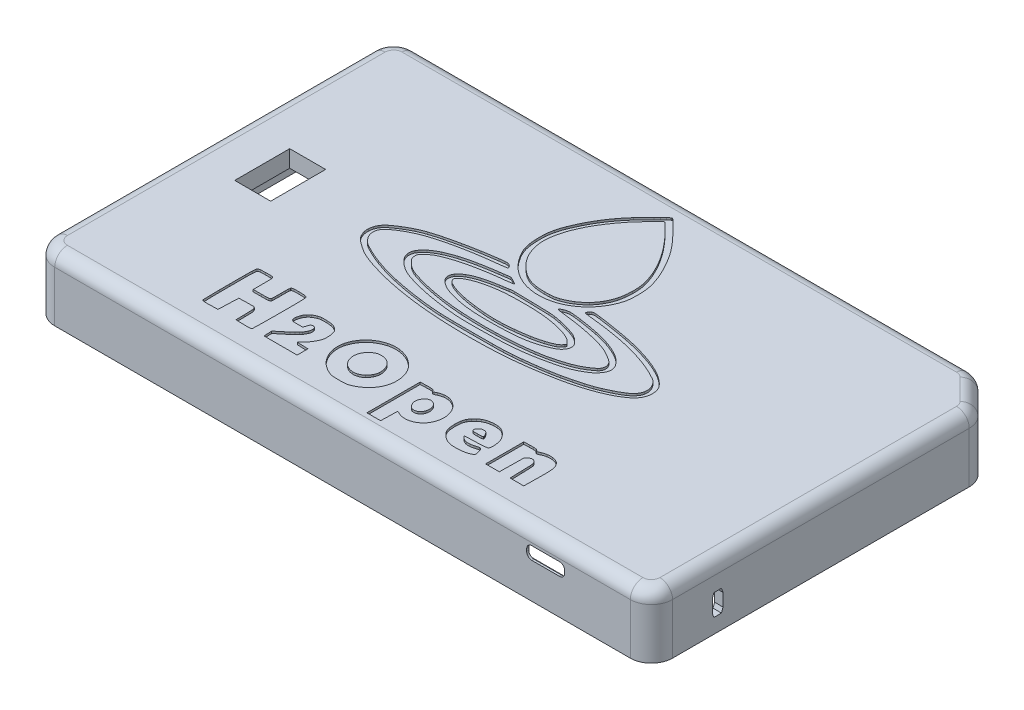
SolidWorks part; units mm, degrees
ref_plane "Front Plane" through (0, 0, 0) normal (0, 0, 1) x (1, 0, 0)
ref_plane "Top Plane" through (0, 0, 0) normal (0, 1, 0) x (1, 0, 0)
ref_plane "Right Plane" through (0, 0, 0) normal (1, 0, 0) x (0, 0, -1)
sketch "Sketch1" plane through (0, 0, 0) normal (0, 1, 0) x (1, 0, 0)
  line L0 (-69.085, -42.56) -> (-69.085, 42.56)
  line L1 (-69.085, 42.56) -> (69.085, 42.56)
  line L2 (-69.085, -42.56) -> (76.995, -42.56)
  line L3 (69.085, 42.56) -> (76.9975, 34.6475)
  line L4 (76.9975, 34.6475) -> (76.995, -42.56)
  point P2 (-69.085, 0)
  point P4 (0, 42.56)
  dimension "D1" = 85.12
  dimension "D2" = 138.17
  dimension "D3" = 146.08
  dimension "D4" = 11.19
  dimension "D5" = 45
extrude "Boss-Extrude1" add sketch "Sketch1" along normal blind 15
sketch "Sketch2" plane through (0, 0, 0) normal (0, -1, 0) x (1, 0, 0)
  line L29 (74.9951, 40.56) -> (-67.085, 40.56)
  line L30 (-67.085, 40.56) -> (-67.085, -40.56)
  line L31 (-67.085, -40.56) -> (68.2566, -40.56)
  line L32 (68.2566, -40.56) -> (74.9975, -33.8191)
  line L33 (74.9975, -33.8191) -> (74.9951, 40.56)
  line L34 (74.9951, 40.56) -> (-67.085, 40.56)
  line L35 (-67.085, 40.56) -> (-67.085, -40.56)
  line L36 (-67.085, -40.56) -> (68.2566, -40.56)
  line L37 (68.2566, -40.56) -> (74.9975, -33.8191)
  line L38 (74.9975, -33.8191) -> (74.9951, 40.56)
  dimension "D1" = 2
extrude "Cut-Extrude1" cut sketch "Sketch2" against normal blind 11
sketch "Sketch3" plane through (0, 11, 0) normal (0, -1, 0) x (1, 0, 0)
  line L0 (74.9951, 40.56) -> (-67.085, 40.56) construction
  line L1 (-67.085, 40.56) -> (-67.085, -40.56) construction
  line L2 (-67.085, -40.56) -> (68.2566, -40.56) construction
  line L3 (74.9975, -33.8191) -> (74.9951, 40.56) construction
  circle A0 centre (-65.585, 39.06) radius 1
  circle A1 centre (-65.585, -39.06) radius 1
  circle A2 centre (73.4951, 39.06) radius 1
  circle A3 centre (-65.585, -39.06) radius 1.375
  circle A4 centre (-65.585, 39.06) radius 1.375
  circle A5 centre (73.4951, 39.06) radius 1.375
  dimension "D1" = 2
  dimension "D6" = 2
  dimension "D7" = 2
  dimension "D10" = 2.75
  dimension "D11" = 2.75
  dimension "D12" = 2.75
  dimension "D2" = 1.5
  dimension "D3" = 1.5
  dimension "D4" = 1.5
  dimension "D5" = 1.5
  dimension "D8" = 1.5
  dimension "D9" = 1.5
extrude "Boss-Extrude7" add sketch "Sketch3" along normal blind 5
fillet "Fillet2" radius 3 5 edges at (-69.085, 15, 0) (0, 15, -42.56) (73.0413, 15, -38.6037) (76.9963, 15, 3.9563) (3.955, 15, 42.56)
fillet "Fillet3" radius 5 10 edges at (-69.085, 6, 42.56) (-68.2063, 14.1213, 41.6813) (-69.085, 6, -42.56) (-68.2063, 14.1213, -41.6813) (69.085, 6, -42.56) (68.721, 14.1213, -41.6813) (76.9975, 6, -34.6475) (76.1188, 14.1213, -34.2835) (76.995, 6, 42.56) (76.1163, 14.1213, 41.6813)
sketch "Sketch4" plane through (0, 15, 0) normal (0, 1, 0) x (1, 0, 0)
  line L0 (-5.2574, 6.3363) -> (-5.9266, 6.2402)
  line L1 (-3.051, 3.67) -> (-3.5719, 3.5824)
  line L2 (-3.5719, 3.5824) -> (-4.1882, 3.4796)
  line L3 (-4.1882, 3.4796) -> (-4.838, 3.3722)
  line L4 (-34.9308, -34.9317) -> (-33.1587, -34.8829)
  line L5 (-33.1587, -34.8829) -> (-33.0736, -32.5016)
  line L6 (-33.0736, -32.5016) -> (-32.9886, -30.1203)
  line L7 (-32.9886, -30.1203) -> (-31.0796, -30.0722)
  line L8 (-28.9481, -32.8418) -> (-28.9063, -34.8829)
  line L9 (-28.9063, -34.8829) -> (-27.1342, -34.9317)
  line L10 (-31.1357, -26.6333) -> (-33.0736, -26.6333)
  line L11 (-33.0736, -26.6333) -> (-33.0736, -24.2702)
  line L12 (-20.7371, -28.5044) -> (-19.4984, -28.5044)
  line L13 (-19.4984, -28.5044) -> (-19.2696, -27.7815)
  line L14 (-20.6874, -31.5828) -> (-22.3736, -32.9615)
  line L15 (-22.3736, -32.9615) -> (-22.3231, -33.9222)
  line L16 (-22.3231, -33.9222) -> (-22.2727, -34.8829)
  line L17 (-22.2727, -34.8829) -> (-18.3605, -34.8829)
  line L18 (-18.3605, -34.8829) -> (-14.4483, -34.8829)
  line L19 (-14.4483, -34.8829) -> (-14.4483, -33.6072)
  line L20 (-14.4483, -33.6072) -> (-14.4483, -32.3315)
  line L21 (-14.4483, -32.3315) -> (-15.757, -32.282)
  line L22 (-15.757, -32.282) -> (-17.0657, -32.2325)
  line L23 (-17.0657, -32.2325) -> (-16.3009, -31.4343)
  line L24 (6.8965, -25.8171) -> (5.6228, -25.8679)
  line L25 (5.6228, -25.8679) -> (5.6228, -32.1614)
  line L26 (5.6228, -32.1614) -> (5.6228, -38.4549)
  line L27 (5.6228, -38.4549) -> (7.2387, -38.4549)
  line L28 (7.2387, -38.4549) -> (8.8546, -38.4549)
  line L29 (8.8546, -38.4549) -> (8.9024, -36.467)
  line L30 (8.9024, -36.467) -> (8.9502, -34.479)
  line L31 (8.9502, -34.479) -> (9.6678, -34.8048)
  line L32 (22.2281, -32.1052) -> (21.7817, -31.6511)
  line L33 (21.7817, -31.6511) -> (24.3715, -31.5617)
  line L34 (31.39, -25.8171) -> (30.1163, -25.8679)
  line L35 (30.1163, -25.8679) -> (30.1163, -30.3754)
  line L36 (30.1163, -30.3754) -> (30.1163, -34.8829)
  line L37 (30.1163, -34.8829) -> (31.7322, -34.8829)
  line L38 (31.7322, -34.8829) -> (33.3481, -34.8829)
  line L39 (33.3481, -34.8829) -> (33.3946, -31.958)
  line L40 (33.3946, -31.958) -> (33.4411, -29.0331)
  line L41 (33.4411, -29.0331) -> (33.8853, -28.6837)
  line L42 (35.8145, -31.9334) -> (35.8995, -34.8829)
  line L43 (35.8995, -34.8829) -> (37.5154, -34.8829)
  line L44 (37.5154, -34.8829) -> (39.1313, -34.8829)
  line L45 (39.1313, -34.8829) -> (39.1776, -31.598)
  arc A0 (-0.4595, 35.4935) -> (-2.8347, 33.0017) centre (37.0957, -2.6811) ccw
  arc A1 (-2.8347, 33.0017) -> (-4.8098, 30.5893) centre (24.077, 8.9527) ccw
  arc A2 (-4.8098, 30.5893) -> (-6.4501, 28.173) centre (20.3393, 11.7523) ccw
  arc A3 (-6.4501, 28.173) -> (-7.817, 25.6706) centre (17.8976, 13.2489) ccw
  arc A4 (-7.817, 25.6706) -> (-8.9328, 23.1457) centre (28.8643, 7.9514) ccw
  arc A5 (-8.9328, 23.1457) -> (-9.5775, 21.1252) centre (4.4879, 17.7506) ccw
  arc A6 (-9.5775, 21.1252) -> (-9.8723, 19.202) centre (1.7861, 18.3988) ccw
  arc A7 (-9.8723, 19.202) -> (-9.895, 17.0096) centre (8.8523, 17.912) ccw
  arc A8 (-9.895, 17.0096) -> (-9.7498, 15.4268) centre (8.4005, 17.8902) ccw
  arc A9 (-9.7498, 15.4268) -> (-9.4745, 14.1492) centre (-1.3714, 16.564) ccw
  arc A10 (-9.4745, 14.1492) -> (-9.0153, 12.9667) centre (-1.9387, 16.3949) ccw
  arc A11 (-9.0153, 12.9667) -> (-8.3071, 11.6811) centre (3.5991, 19.0776) ccw
  arc A12 (-8.3071, 11.6811) -> (-5.8028, 8.7365) centre (2.7617, 18.5574) ccw
  arc A13 (-5.8028, 8.7365) -> (-2.6147, 6.7622) centre (1.8048, 17.4601) ccw
  arc A14 (-2.6147, 6.7622) -> (1.0074, 5.9243) centre (1.7209, 17.2571) ccw
  arc A15 (1.0074, 5.9243) -> (4.7723, 6.2777) centre (1.7698, 18.0338) ccw
  arc A16 (4.7723, 6.2777) -> (7.6262, 7.4513) centre (2.0379, 16.9842) ccw
  arc A17 (7.6262, 7.4513) -> (10.1362, 9.3954) centre (1.3767, 18.112) ccw
  arc A18 (10.1362, 9.3954) -> (12.0768, 11.9237) centre (1.306, 18.1823) ccw
  arc A19 (12.0768, 11.9237) -> (13.2619, 14.8091) centre (2.1795, 17.6748) ccw
  arc A20 (13.2619, 14.8091) -> (13.48, 16.1336) centre (6.0188, 16.682) ccw
  arc A21 (13.48, 16.1336) -> (13.5333, 17.8646) centre (-6.8001, 17.6242) ccw
  arc A22 (13.5333, 17.8646) -> (13.4372, 19.6304) centre (-7.2502, 17.6189) ccw
  arc A23 (13.4372, 19.6304) -> (13.1878, 21.0781) centre (3.5032, 18.6645) ccw
  arc A24 (13.1878, 21.0781) -> (12.3014, 23.7653) centre (-5.2881, 16.4735) ccw
  arc A25 (12.3014, 23.7653) -> (10.921, 26.6679) centre (-16.859, 11.6766) ccw
  arc A26 (10.921, 26.6679) -> (9.1974, 29.5141) centre (-18.5827, 10.7465) ccw
  arc A27 (9.1974, 29.5141) -> (7.2741, 32.0366) centre (-13.7614, 14.0036) ccw
  arc A28 (7.2741, 32.0366) -> (5.8496, 33.6168) centre (-25.1101, 4.2749) ccw
  arc A29 (5.8496, 33.6168) -> (4.0289, 35.4863) centre (-63.6677, -32.2677) ccw
  arc A30 (4.0289, 35.4863) -> (2.1418, 37.3578) centre (-250.3747, -219.1327) ccw
  arc A31 (2.1418, 37.3578) -> (1.814, 37.4921) centre (1.814, 37.0248) ccw
  arc A32 (1.814, 37.4921) -> (1.659, 37.4351) centre (1.814, 37.2531) ccw
  arc A33 (1.659, 37.4351) -> (1.0463, 36.9051) centre (34.8824, -1.5848) ccw
  arc A34 (1.0463, 36.9051) -> (0.3366, 36.2595) centre (19.7627, 15.6143) ccw
  arc A35 (0.3366, 36.2595) -> (-0.4595, 35.4935) centre (34.3898, 0.0694) ccw
  arc A36 (6.8922, 30.3683) -> (4.1356, 33.512) centre (-25.4447, 4.7929) ccw
  arc A37 (9.1405, 27.14) -> (6.8922, 30.3683) centre (-18.4766, 10.304) ccw
  arc A38 (10.8178, 23.9301) -> (9.1405, 27.14) centre (-14.3218, 12.8368) ccw
  arc A39 (11.8592, 20.8425) -> (10.8178, 23.9301) centre (-5.7175, 16.6336) ccw
  arc A40 (12.0817, 19.4539) -> (11.8592, 20.8425) centre (2.8696, 18.6898) ccw
  arc A41 (12.1348, 17.8343) -> (12.0817, 19.4539) centre (-4.0803, 18.1134) ccw
  arc A42 (12.0255, 16.2048) -> (12.1348, 17.8343) centre (-4.2782, 18.1168) ccw
  arc A43 (11.7549, 14.7846) -> (12.0255, 16.2048) centre (1.9792, 17.383) ccw
  arc A44 (10.8132, 12.4546) -> (11.7549, 14.7846) centre (1.9614, 17.3877) ccw
  arc A45 (9.33, 10.4384) -> (10.8132, 12.4546) centre (2.1011, 17.3098) ccw
  arc A46 (7.3704, 8.8318) -> (9.33, 10.4384) centre (1.9075, 17.4939) ccw
  arc A47 (5.0275, 7.7071) -> (7.3704, 8.8318) centre (1.335, 18.4016) ccw
  arc A48 (4.3672, 7.5131) -> (5.0275, 7.7071) centre (2.6162, 14.691) ccw
  arc A49 (3.7405, 7.3987) -> (4.3672, 7.5131) centre (3.08, 12.7895) ccw
  arc A50 (2.9852, 7.3404) -> (3.7405, 7.3987) centre (2.7142, 15.7758) ccw
  arc A51 (1.8807, 7.3216) -> (2.9852, 7.3404) centre (1.8126, 43.8304) ccw
  arc A52 (-0.3703, 7.4791) -> (1.8807, 7.3216) centre (1.8514, 23.0628) ccw
  arc A53 (-2.2067, 7.9688) -> (-0.3703, 7.4791) centre (0.7597, 15.4053) ccw
  arc A54 (-3.854, 8.87) -> (-2.2067, 7.9688) centre (0.6742, 15.1909) ccw
  arc A55 (-5.5285, 10.2771) -> (-3.854, 8.87) centre (4.4054, 20.3993) ccw
  arc A56 (-6.57, 11.4531) -> (-5.5285, 10.2771) centre (2.3393, 18.2941) ccw
  arc A57 (-7.4124, 12.7385) -> (-6.57, 11.4531) centre (1.5979, 17.7247) ccw
  arc A58 (-8.0561, 14.1385) -> (-7.4124, 12.7385) centre (1.6471, 17.752) ccw
  arc A59 (-8.5051, 15.6559) -> (-8.0561, 14.1385) centre (2.732, 18.156) ccw
  arc A60 (-8.6407, 18.9739) -> (-8.5051, 15.6559) centre (0.6439, 17.6914) ccw
  arc A61 (-7.683, 22.7925) -> (-8.6407, 18.9739) centre (9.3725, 16.4857) ccw
  arc A62 (-5.7089, 26.9071) -> (-7.683, 22.7925) centre (15.3212, 14.2861) ccw
  arc A63 (-2.7893, 31.1136) -> (-5.7089, 26.9071) centre (27.4741, 6.9926) ccw
  arc A64 (-1.6542, 32.4489) -> (-2.7893, 31.1136) centre (18.9013, 13.8255) ccw
  arc A65 (-0.1494, 34.057) -> (-1.6542, 32.4489) centre (49.0221, -13.4642) ccw
  arc A66 (1.4147, 35.6592) -> (-0.1494, 34.057) centre (160.0912, -120.8057) ccw
  arc A67 (1.7316, 35.7915) -> (1.4147, 35.6592) centre (1.7309, 35.3474) ccw
  arc A68 (1.8565, 35.7422) -> (1.7316, 35.7915) centre (1.7313, 35.6079) ccw
  arc A69 (2.5166, 35.1218) -> (1.8565, 35.7422) centre (-68.5112, -39.7839) ccw
  arc A70 (3.2736, 34.3857) -> (2.5166, 35.1218) centre (-26.292, 4.7404) ccw
  arc A71 (4.1356, 33.512) -> (3.2736, 34.3857) centre (-50.5037, -19.5365) ccw
  arc A72 (-10.281, 8.7249) -> (-14.04, 8.14) centre (2.4744, -85.6277) ccw
  arc A73 (-14.04, 8.14) -> (-17.9052, 7.3872) centre (4.9152, -99.4861) ccw
  arc A74 (-17.9052, 7.3872) -> (-21.4596, 6.5585) centre (2.4659, -88.0155) ccw
  arc A75 (-21.4596, 6.5585) -> (-24.2287, 5.7467) centre (-11.9922, -30.8649) ccw
  arc A76 (-24.2287, 5.7467) -> (-26.3389, 4.8847) centre (-18.6883, -10.8302) ccw
  arc A77 (-26.3389, 4.8847) -> (-28.4962, 3.6928) centre (-15.8971, -16.5634) ccw
  arc A78 (-28.4962, 3.6928) -> (-30.3254, 2.4213) centre (-16.9639, -14.8483) ccw
  arc A79 (-30.3254, 2.4213) -> (-31.2802, 1.3608) centre (-27.877, -0.7432) ccw
  arc A80 (-31.2802, 1.3608) -> (-31.7081, 0.4247) centre (-27.7691, -0.81) ccw
  arc A81 (-31.7081, 0.4247) -> (-31.8845, -0.5771) centre (-27.9473, -0.7541) ccw
  arc A82 (-31.8845, -0.5771) -> (-31.799, -1.5956) centre (-27.9059, -0.756) ccw
  arc A83 (-31.799, -1.5956) -> (-31.4574, -2.5809) centre (-27.5863, -0.687) ccw
  arc A84 (-31.4574, -2.5809) -> (-31.1582, -3.1079) centre (-27.0237, -0.4117) ccw
  arc A85 (-31.1582, -3.1079) -> (-30.8233, -3.5374) centre (-28.4508, -1.3424) ccw
  arc A86 (-30.8233, -3.5374) -> (-30.3676, -3.9673) centre (-27.4372, -0.4046) ccw
  arc A87 (-30.3676, -3.9673) -> (-29.672, -4.5107) centre (-19.2224, 9.5826) ccw
  arc A88 (-29.672, -4.5107) -> (-28.2225, -5.5093) centre (-14.5806, 15.843) ccw
  arc A89 (-28.2225, -5.5093) -> (-26.9174, -6.2434) centre (-21.0399, 5.7329) ccw
  arc A90 (-26.9174, -6.2434) -> (-25.4486, -6.8738) centre (-19.9859, 7.8807) ccw
  arc A91 (-25.4486, -6.8738) -> (-23.4633, -7.5577) centre (-9.4923, 36.2237) ccw
  arc A92 (-23.4633, -7.5577) -> (-18.0285, -8.995) centre (-6.4865, 45.6431) ccw
  arc A93 (-18.0285, -8.995) -> (-11.9985, -10.0242) centre (-1.8677, 67.5078) ccw
  arc A94 (-11.9985, -10.0242) -> (-5.4092, -10.6438) centre (-0.1434, 80.7039) ccw
  arc A95 (-5.4092, -10.6438) -> (1.7106, -10.8471) centre (1.6494, 111.806) ccw
  arc A96 (1.7106, -10.8471) -> (5.9608, -10.7864) centre (1.6338, 143.505) ccw
  arc A97 (5.9608, -10.7864) -> (9.6747, -10.6059) centre (3.421, 79.7789) ccw
  arc A98 (9.6747, -10.6059) -> (13.2293, -10.2827) centre (3.9727, 71.805) ccw
  arc A99 (13.2293, -10.2827) -> (16.989, -9.79) centre (1.4412, 94.253) ccw
  arc A100 (16.989, -9.79) -> (22.1672, -8.8525) centre (4.3476, 74.803) ccw
  arc A101 (22.1672, -8.8525) -> (26.5393, -7.6979) centre (12.4101, 36.9529) ccw
  arc A102 (26.5393, -7.6979) -> (30.1705, -6.3191) centre (16.1541, 25.1212) ccw
  arc A103 (30.1705, -6.3191) -> (33.0852, -4.6965) centre (22.4945, 10.8989) ccw
  arc A104 (33.0852, -4.6965) -> (34.1565, -3.8282) centre (28.4971, 2.0598) ccw
  arc A105 (34.1565, -3.8282) -> (34.8978, -2.9001) centre (31.0107, -0.5554) ccw
  arc A106 (34.8978, -2.9001) -> (35.3273, -1.8806) centre (31.6001, -0.9109) ccw
  arc A107 (35.3273, -1.8806) -> (35.4706, -0.742) centre (31.0219, -0.7605) ccw
  arc A108 (35.4706, -0.742) -> (35.3822, 0.0959) centre (31.287, -0.7594) ccw
  arc A109 (35.3822, 0.0959) -> (35.1279, 0.853) centre (32.0662, -0.5966) ccw
  arc A110 (35.1279, 0.853) -> (34.6913, 1.5575) centre (31.7968, -0.7242) ccw
  arc A111 (34.6913, 1.5575) -> (34.0591, 2.2391) centre (30.1364, -2.0331) ccw
  arc A112 (34.0591, 2.2391) -> (30.961, 4.3475) centre (25.3019, -7.2983) ccw
  arc A113 (30.961, 4.3475) -> (26.5509, 6.1065) centre (16.7006, -24.9987) ccw
  arc A114 (26.5509, 6.1065) -> (20.7903, 7.5705) centre (11.0238, -42.9249) ccw
  arc A115 (20.7903, 7.5705) -> (13.4731, 8.7582) centre (-2.5689, -113.202) ccw
  arc A116 (13.4731, 8.7582) -> (12.6863, 8.8499) centre (9.989, -17.7303) ccw
  arc A117 (12.6863, 8.8499) -> (12.1898, 8.8725) centre (12.2349, 4.402) ccw
  arc A118 (12.1898, 8.8725) -> (11.8401, 8.8374) centre (12.2095, 6.9169) ccw
  arc A119 (11.8401, 8.8374) -> (11.5624, 8.7389) centre (12.0255, 7.8736) ccw
  arc A120 (11.5624, 8.7389) -> (11.299, 8.5388) centre (12.0571, 7.8146) ccw
  arc A121 (11.299, 8.5388) -> (11.0867, 8.2514) centre (12.3242, 7.5594) ccw
  arc A122 (11.0867, 8.2514) -> (10.9787, 7.9688) centre (12.0013, 7.74) ccw
  arc A123 (10.9787, 7.9688) -> (11.031, 7.7888) centre (11.1686, 7.9263) ccw
  arc A124 (11.031, 7.7888) -> (11.106, 7.7514) centre (11.1242, 7.882) ccw
  arc A125 (11.106, 7.7514) -> (11.7811, 7.6592) centre (29.4212, 139.251) ccw
  arc A126 (11.7811, 7.6592) -> (12.5607, 7.5618) centre (17.5733, 50.8676) ccw
  arc A127 (12.5607, 7.5618) -> (13.4704, 7.4618) centre (21.7661, 87.09) ccw
  arc A128 (21.1007, 6.2916) -> (13.4704, 7.4618) centre (5.1981, -71.9412) ccw
  arc A129 (27.5638, 4.4766) -> (21.1007, 6.2916) centre (11.9628, -38.6618) ccw
  arc A130 (32.3056, 2.2998) -> (27.5638, 4.4766) centre (16.9065, -24.9919) ccw
  arc A131 (34.0902, 0.0046) -> (32.3056, 2.2998) centre (30.4546, -0.9808) ccw
  arc A132 (34.1272, -1.3359) -> (34.0902, 0.0046) centre (31.3346, -0.7423) ccw
  arc A133 (33.5498, -2.5567) -> (34.1272, -1.3359) centre (31.2586, -0.7261) ccw
  arc A134 (32.2657, -3.7209) -> (33.5498, -2.5567) centre (29.3057, 0.8342) ccw
  arc A135 (30.1648, -4.9083) -> (32.2657, -3.7209) centre (21.6236, 12.656) ccw
  arc A136 (28.4435, -5.7017) -> (30.1648, -4.9083) centre (10.1607, 36.2283) ccw
  arc A137 (26.9841, -6.2759) -> (28.4435, -5.7017) centre (19.8131, 14.0913) ccw
  arc A138 (25.3757, -6.7844) -> (26.9841, -6.2759) centre (18.3194, 18.3338) ccw
  arc A139 (23.1425, -7.3808) -> (25.3757, -6.7844) centre (1.1626, 79.4068) ccw
  arc A140 (20.8165, -7.9245) -> (23.1425, -7.3808) centre (7.2173, 55.4996) ccw
  arc A141 (18.558, -8.3602) -> (20.8165, -7.9245) centre (9.122, 46.6165) ccw
  arc A142 (16.0497, -8.7441) -> (18.558, -8.3602) centre (6.7042, 60.7032) ccw
  arc A143 (12.9368, -9.1324) -> (16.0497, -8.7441) centre (-5.5831, 152.0106) ccw
  arc A144 (10.8637, -9.3332) -> (12.9368, -9.1324) centre (6.2845, 48.7499) ccw
  arc A145 (8.9316, -9.4423) -> (10.8637, -9.3332) centre (7.4496, 33.9705) ccw
  arc A146 (6.392, -9.4937) -> (8.9316, -9.4423) centre (5.8084, 82.0481) ccw
  arc A147 (1.8807, -9.5098) -> (6.392, -9.4937) centre (1.2641, 794.9428) ccw
  arc A148 (-3.0222, -9.4921) -> (1.8807, -9.5098) centre (1.4523, 550.1841) ccw
  arc A149 (-5.9769, -9.4146) -> (-3.0222, -9.4921) centre (-2.3742, 71.5534) ccw
  arc A150 (-8.4224, -9.2434) -> (-5.9769, -9.4146) centre (-3.8318, 38.793) ccw
  arc A151 (-11.3016, -8.9233) -> (-8.4224, -9.2434) centre (0.4852, 83.9665) ccw
  arc A152 (-18.2045, -7.7303) -> (-11.3016, -8.9233) centre (-1.4824, 68.4601) ccw
  arc A153 (-24.0556, -6.0225) -> (-18.2045, -7.7303) centre (-8.5794, 36.1242) ccw
  arc A154 (-28.4326, -4.0187) -> (-24.0556, -6.0225) centre (-13.3278, 23.1928) ccw
  arc A155 (-30.4164, -1.9044) -> (-28.4326, -4.0187) centre (-26.1299, 0.1297) ccw
  arc A156 (-30.6104, -1.337) -> (-30.4164, -1.9044) centre (-28.0274, -0.7707) ccw
  arc A157 (-30.6811, -0.7191) -> (-30.6104, -1.337) centre (-27.6233, -0.6821) ccw
  arc A158 (-30.6253, -0.1182) -> (-30.6811, -0.7191) centre (-27.7959, -0.6842) ccw
  arc A159 (-30.4442, 0.398) -> (-30.6253, -0.1182) centre (-28.7022, -0.5029) ccw
  arc A160 (-29.6135, 1.4245) -> (-30.4442, 0.398) centre (-27.5365, -1.1057) ccw
  arc A161 (-27.9974, 2.5874) -> (-29.6135, 1.4245) centre (-19.6789, -10.6779) ccw
  arc A162 (-25.9444, 3.7108) -> (-27.9974, 2.5874) centre (-17.5268, -14.1098) ccw
  arc A163 (-23.6772, 4.6415) -> (-25.9444, 3.7108) centre (-15.8278, -17.7065) ccw
  arc A164 (-20.9116, 5.4815) -> (-23.6772, 4.6415) centre (-12.5069, -27.1616) ccw
  arc A165 (-17.5012, 6.2717) -> (-20.9116, 5.4815) centre (-2.9605, -64.2387) ccw
  arc A166 (-13.7527, 6.9556) -> (-17.5012, 6.2717) centre (-0.7163, -75.1213) ccw
  arc A167 (-9.9408, 7.4742) -> (-13.7527, 6.9556) centre (-0.2084, -78.3191) ccw
  arc A168 (-9.9408, 7.4742) -> (-8.9854, 7.5912) centre (-16.0361, 61.2052) ccw
  arc A169 (-8.9854, 7.5912) -> (-8.1576, 7.7115) centre (-13.0192, 38.2644) ccw
  arc A170 (-8.1576, 7.7115) -> (-7.4561, 7.8273) centre (-17.6847, 67.5851) ccw
  arc A171 (-7.4561, 7.8273) -> (-7.3338, 7.8891) centre (-7.4955, 8.0576) ccw
  arc A172 (-7.3338, 7.8891) -> (-7.3102, 7.9716) centre (-7.3928, 7.9506) ccw
  arc A173 (-7.3102, 7.9716) -> (-7.3654, 8.1155) centre (-7.9486, 7.809) ccw
  arc A174 (-7.3654, 8.1155) -> (-7.4784, 8.2895) centre (-8.3628, 7.5914) ccw
  arc A175 (-7.4784, 8.2895) -> (-7.6391, 8.4702) centre (-9.0998, 7.0096) ccw
  arc A176 (-7.6391, 8.4702) -> (-8.0198, 8.752) centre (-8.7734, 7.336) ccw
  arc A177 (-8.0198, 8.752) -> (-8.4312, 8.8759) centre (-8.5368, 7.7805) ccw
  arc A178 (-8.4312, 8.8759) -> (-9.0457, 8.8733) centre (-8.7253, 5.8252) ccw
  arc A179 (-9.0457, 8.8733) -> (-10.281, 8.7249) centre (-4.6571, -32.876) ccw
  arc A180 (-7.5595, 6.0114) -> (-12.0847, 5.2561) centre (3.4108, -73.6507) ccw
  arc A181 (-12.0847, 5.2561) -> (-15.6777, 4.3482) centre (-5.4189, -28.6875) ccw
  arc A182 (-15.6777, 4.3482) -> (-18.4966, 3.2622) centre (-8.951, -17.3133) ccw
  arc A183 (-18.4966, 3.2622) -> (-20.6197, 1.9557) centre (-14.0127, -6.4027) ccw
  arc A184 (-20.6197, 1.9557) -> (-21.8796, 0.4622) centre (-17.5876, -1.8802) ccw
  arc A185 (-21.8796, 0.4622) -> (-22.134, -1.131) centre (-19.7638, -0.6925) ccw
  arc A186 (-22.134, -1.131) -> (-21.3195, -2.7641) centre (-18.8837, -0.5297) ccw
  arc A187 (-21.3195, -2.7641) -> (-19.4504, -4.3647) centre (-13.7684, 4.1626) ccw
  arc A188 (-19.4504, -4.3647) -> (-17.1629, -5.4857) centre (-14.0873, 3.6839) ccw
  arc A189 (-17.1629, -5.4857) -> (-13.58, -6.513) centre (-3.8073, 34.3324) ccw
  arc A190 (-13.58, -6.513) -> (-9.2618, -7.3608) centre (-1.0893, 45.6924) ccw
  arc A191 (-9.2618, -7.3608) -> (-4.5622, -7.9268) centre (1.6689, 63.598) ccw
  arc A192 (-4.5622, -7.9268) -> (-1.3485, -8.0808) centre (-0.9839, 33.1469) ccw
  arc A193 (-1.3485, -8.0808) -> (3.1202, -8.0532) centre (-0.0328, 140.6808) ccw
  arc A194 (3.1202, -8.0532) -> (7.6353, -7.889) centre (-0.0383, 140.9347) ccw
  arc A195 (7.6353, -7.889) -> (11.0457, -7.5959) centre (5.0573, 42.1086) ccw
  arc A196 (11.0457, -7.5959) -> (13.3937, -7.2533) centre (5.3712, 39.5026) ccw
  arc A197 (13.3937, -7.2533) -> (15.941, -6.7657) centre (1.9569, 59.4017) ccw
  arc A198 (15.941, -6.7657) -> (18.3139, -6.2158) centre (2.9934, 54.4973) ccw
  arc A199 (18.3139, -6.2158) -> (20.0808, -5.6864) centre (13.1745, 14.1507) ccw
  arc A200 (20.0808, -5.6864) -> (21.3331, -5.1835) centre (15.348, 7.9078) ccw
  arc A201 (21.3331, -5.1835) -> (22.6118, -4.5371) centre (13.7324, 11.4417) ccw
  arc A202 (22.6118, -4.5371) -> (23.7437, -3.847) centre (14.6165, 9.8507) ccw
  arc A203 (23.7437, -3.847) -> (24.5218, -3.2186) centre (20.7152, 0.6981) ccw
  arc A204 (24.5218, -3.2186) -> (25.4684, -1.9631) centre (20.9396, 0.4672) ccw
  arc A205 (25.4684, -1.9631) -> (25.7514, -0.7073) centre (23.349, -0.8258) ccw
  arc A206 (25.7514, -0.7073) -> (25.3486, 0.544) centre (23.2181, -0.8322) ccw
  arc A207 (25.3486, 0.544) -> (24.2749, 1.7861) centre (20.3816, -2.6645) ccw
  arc A208 (24.2749, 1.7861) -> (22.2432, 3.148) centre (17.976, -5.4145) ccw
  arc A209 (22.2432, 3.148) -> (19.498, 4.2755) centre (13.1227, -15.1528) ccw
  arc A210 (19.498, 4.2755) -> (16.001, 5.1986) centre (9.9333, -24.8725) ccw
  arc A211 (16.001, 5.1986) -> (11.6471, 5.9299) centre (2.6492, -60.9715) ccw
  arc A212 (11.6471, 5.9299) -> (9.9707, 6.1343) centre (2.5314, -61.8472) ccw
  arc A213 (9.9707, 6.1343) -> (9.0532, 6.1733) centre (9.2186, -0.7385) ccw
  arc A214 (9.0532, 6.1733) -> (8.3717, 6.0804) centre (9.1271, 3.0867) ccw
  arc A215 (8.3717, 6.0804) -> (7.6578, 5.8344) centre (9.4641, 1.7508) ccw
  arc A216 (7.6578, 5.8344) -> (7.1191, 5.5401) centre (9.1445, 2.4734) ccw
  arc A217 (7.1191, 5.5401) -> (7.1232, 5.3538) centre (7.1798, 5.4482) ccw
  arc A218 (7.1232, 5.3538) -> (7.5431, 5.2059) centre (7.6958, 6.3096) ccw
  arc A219 (7.5431, 5.2059) -> (9.0247, 5.0156) centre (18.1006, 81.5241) ccw
  arc A220 (12.1789, 4.5767) -> (9.0247, 5.0156) centre (-0.2651, -73.295) ccw
  arc A221 (15.1818, 4.0259) -> (12.1789, 4.5767) centre (1.6681, -61.197) ccw
  arc A222 (17.8376, 3.4067) -> (15.1818, 4.0259) centre (4.0137, -49.8761) ccw
  arc A223 (19.9107, 2.7601) -> (17.8376, 3.4067) centre (12.2118, -18.2772) ccw
  arc A224 (21.1465, 2.2313) -> (19.9107, 2.7601) centre (15.5901, -9.046) ccw
  arc A225 (22.4199, 1.5351) -> (21.1465, 2.2313) centre (13.6048, -13.0755) ccw
  arc A226 (23.5104, 0.8146) -> (22.4199, 1.5351) centre (14.1752, -12.1301) ccw
  arc A227 (24.0726, 0.2491) -> (23.5104, 0.8146) centre (22.0786, -1.1708) ccw
  arc A228 (23.7576, -2.1305) -> (24.0726, 0.2491) centre (22.639, -0.7718) ccw
  arc A229 (19.8149, -4.3757) -> (23.7576, -2.1305) centre (15.2922, 8.1515) ccw
  arc A230 (13.0038, -6.0785) -> (19.8149, -4.3757) centre (8.048, 28.2166) ccw
  arc A231 (4.5172, -6.8111) -> (13.0038, -6.0785) centre (2.3856, 67.4019) ccw
  arc A232 (-3.8071, -6.6762) -> (4.5172, -6.8111) centre (1.8557, 85.8458) ccw
  arc A233 (-11.2072, -5.7576) -> (-3.8071, -6.6762) centre (-0.1533, 53.0225) ccw
  arc A234 (-17.0521, -4.2347) -> (-11.2072, -5.7576) centre (-3.1111, 37.2941) ccw
  arc A235 (-20.1585, -2.1708) -> (-17.0521, -4.2347) centre (-14.7657, 2.5762) ccw
  arc A236 (-20.5076, -1.7431) -> (-20.1585, -2.1708) centre (-14.601, 2.7212) ccw
  arc A237 (-20.7, -1.419) -> (-20.5076, -1.7431) centre (-19.1552, -0.721) ccw
  arc A238 (-20.7956, -1.0974) -> (-20.7, -1.419) centre (-19.5672, -0.9072) ccw
  arc A239 (-20.8269, -0.6917) -> (-20.7956, -1.0974) centre (-18.1762, -0.6917) ccw
  arc A240 (-20.7972, -0.2755) -> (-20.8269, -0.6917) centre (-17.8926, -0.6917) ccw
  arc A241 (-20.7024, 0.0185) -> (-20.7972, -0.2755) centre (-19.8914, -0.4053) ccw
  arc A242 (-20.5021, 0.2994) -> (-20.7024, 0.0185) centre (-19.5898, -0.5628) ccw
  arc A243 (-20.104, 0.6919) -> (-20.5021, 0.2994) centre (-14.7637, -5.1239) ccw
  arc A244 (-19.3429, 1.327) -> (-20.104, 0.6919) centre (-13.0164, -7.0267) ccw
  arc A245 (-18.6139, 1.8033) -> (-19.3429, 1.327) centre (-15.5591, -3.6693) ccw
  arc A246 (-17.7342, 2.2293) -> (-18.6139, 1.8033) centre (-14.5156, -5.5386) ccw
  arc A247 (-16.4724, 2.719) -> (-17.7342, 2.2293) centre (-6.2592, -25.4651) ccw
  arc A248 (-14.2172, 3.4247) -> (-16.4724, 2.719) centre (-7.4007, -22.3151) ccw
  arc A249 (-11.5115, 4.0625) -> (-14.2172, 3.4247) centre (-1.2278, -45.6246) ccw
  arc A250 (-8.5188, 4.6027) -> (-11.5115, 4.0625) centre (0.5813, -54.3658) ccw
  arc A251 (-5.3865, 5.0134) -> (-8.5188, 4.6027) centre (2.0765, -64.0541) ccw
  arc A252 (-5.3865, 5.0134) -> (-4.6457, 5.1021) centre (-8.8744, 37.2926) ccw
  arc A253 (-4.6457, 5.1021) -> (-4.0088, 5.1973) centre (-7.0007, 23.029) ccw
  arc A254 (-4.0088, 5.1973) -> (-3.4729, 5.2916) centre (-9.7571, 39.4567) ccw
  arc A255 (-3.4729, 5.2916) -> (-3.3897, 5.3485) centre (-3.4954, 5.4138) ccw
  arc A256 (-3.3897, 5.3485) -> (-3.418, 5.4588) centre (-3.4569, 5.39) ccw
  arc A257 (-3.418, 5.4588) -> (-4.2338, 5.9106) centre (-32.4539, -46.0082) ccw
  arc A258 (-4.2338, 5.9106) -> (-5.05, 6.3444) centre (-27.775, -37.4001) ccw
  arc A259 (-5.05, 6.3444) -> (-5.2254, 6.3463) centre (-5.1395, 6.172) ccw
  arc A260 (-5.2574, 6.3363) -> (-5.2254, 6.3463) centre (-5.2726, 6.4422) ccw
  arc A261 (-6.6764, 6.134) -> (-5.9266, 6.2402) centre (-36.6885, 220.6537) ccw
  arc A262 (-7.5595, 6.0114) -> (-6.6764, 6.134) centre (-64.0785, 416.4306) ccw
  arc A263 (-3.051, 3.67) -> (-2.7969, 3.7141) centre (-7.6362, 30.8191) ccw
  arc A264 (-4.838, 3.3722) -> (-8.4772, 2.5764) centre (0.9661, -31.8882) ccw
  arc A265 (-8.4772, 2.5764) -> (-11.0116, 1.5232) centre (-5.6015, -7.919) ccw
  arc A266 (-11.0116, 1.5232) -> (-12.4347, 0.2603) centre (-8.6936, -2.5222) ccw
  arc A267 (-12.4347, 0.2603) -> (-12.7651, -1.1698) centre (-10.9658, -0.8322) ccw
  arc A268 (-12.7651, -1.1698) -> (-12.4202, -1.9139) centre (-11.1262, -0.8623) ccw
  arc A269 (-12.4202, -1.9139) -> (-11.6446, -2.677) centre (-8.6152, 1.1782) ccw
  arc A270 (-11.6446, -2.677) -> (-10.5559, -3.3755) centre (-7.4553, 2.6543) ccw
  arc A271 (-10.5559, -3.3755) -> (-9.2557, -3.9274) centre (-6.1611, 5.1712) ccw
  arc A272 (-9.2557, -3.9274) -> (-6.6925, -4.6331) centre (-2.0196, 17.3477) ccw
  arc A273 (-6.6925, -4.6331) -> (-3.9355, -5.0733) centre (-1.0134, 22.0807) ccw
  arc A274 (-3.9355, -5.0733) -> (-0.7253, -5.2797) centre (0.0698, 32.1464) ccw
  arc A275 (-0.7253, -5.2797) -> (3.2415, -5.2722) centre (1.0956, 80.4386) ccw
  arc A276 (3.2415, -5.2722) -> (6.0992, -5.1584) centre (0.8158, 91.6141) ccw
  arc A277 (6.0992, -5.1584) -> (8.2712, -4.9685) centre (4.2823, 28.1211) ccw
  arc A278 (8.2712, -4.9685) -> (10.0914, -4.6733) centre (5.5648, 17.4817) ccw
  arc A279 (10.0914, -4.6733) -> (11.8283, -4.2371) centre (6.0629, 15.0436) ccw
  arc A280 (11.8283, -4.2371) -> (14.8906, -2.9876) centre (6.9292, 12.1464) ccw
  arc A281 (14.8906, -2.9876) -> (16.2891, -1.456) centre (13.469, -0.2852) ccw
  arc A282 (16.2891, -1.456) -> (16.0763, 0.1558) centre (14.7905, -0.8339) ccw
  arc A283 (16.0763, 0.1558) -> (14.2919, 1.6968) centre (11.4301, -3.4205) ccw
  arc A284 (14.2919, 1.6968) -> (13.2252, 2.1791) centre (10.9374, -4.3015) ccw
  arc A285 (13.2252, 2.1791) -> (11.6354, 2.6862) centre (4.1564, -23.5102) ccw
  arc A286 (11.6354, 2.6862) -> (9.841, 3.1407) centre (3.1638, -26.9872) ccw
  arc A287 (9.841, 3.1407) -> (8.084, 3.4691) centre (4.0339, -23.0614) ccw
  arc A288 (8.084, 3.4691) -> (6.5766, 3.6075) centre (6.1777, -9.0184) ccw
  arc A289 (6.5766, 3.6075) -> (2.4769, 3.7184) centre (-7.6997, -448.2486) ccw
  arc A290 (2.4769, 3.7184) -> (-1.7352, 3.7996) centre (-12.1488, -645.8426) ccw
  arc A291 (-1.7352, 3.7996) -> (-2.7969, 3.7141) centre (-1.8239, -1.7356) ccw
  arc A292 (10.0279, 1.7628) -> (7.694, 2.1783) centre (2.9258, -31.3661) ccw
  arc A293 (12.0168, 1.2245) -> (10.0279, 1.7628) centre (5.9589, -17.2175) ccw
  arc A294 (13.5899, 0.5977) -> (12.0168, 1.2245) centre (7.7371, -11.8041) ccw
  arc A295 (14.6091, -0.0933) -> (13.5899, 0.5977) centre (11.8862, -3.0123) ccw
  arc A296 (15.0323, -0.5025) -> (14.6091, -0.0933) centre (3.5203, -11.9811) ccw
  arc A297 (15.1542, -0.6932) -> (15.0323, -0.5025) centre (14.6571, -0.8766) ccw
  arc A298 (15.1488, -0.8716) -> (15.1542, -0.6932) centre (14.9303, -0.7758) ccw
  arc A299 (14.9986, -1.1489) -> (15.1488, -0.8716) centre (13.4171, -0.1126) ccw
  arc A300 (13.9933, -2.0307) -> (14.9986, -1.1489) centre (12.9073, 0.2214) ccw
  arc A301 (12.0193, -2.8057) -> (13.9933, -2.0307) centre (7.8656, 10.6758) ccw
  arc A302 (9.3388, -3.4516) -> (12.0193, -2.8057) centre (5.5117, 18.3156) ccw
  arc A303 (6.0103, -3.9182) -> (9.3388, -3.4516) centre (0.964, 44.1817) ccw
  arc A304 (3.4937, -4.1181) -> (6.0103, -3.9182) centre (0.7937, 45.8049) ccw
  arc A305 (1.2244, -4.162) -> (3.4937, -4.1181) centre (1.7269, 28.5491) ccw
  arc A306 (-1.0735, -4.0483) -> (1.2244, -4.162) centre (1.7428, 29.5871) ccw
  arc A307 (-3.679, -3.7694) -> (-1.0735, -4.0483) centre (3.6548, 52.4224) ccw
  arc A308 (-6.5756, -3.2861) -> (-3.679, -3.7694) centre (1.6716, 37.2267) ccw
  arc A309 (-8.9308, -2.6535) -> (-6.5756, -3.2861) centre (-2.6229, 16.1311) ccw
  arc A310 (-10.6605, -1.9307) -> (-8.9308, -2.6535) centre (-4.7742, 9.7246) ccw
  arc A311 (-11.4499, -1.1598) -> (-10.6605, -1.9307) centre (-9.8346, -0.2953) ccw
  arc A312 (-11.3054, -0.2863) -> (-11.4499, -1.1598) centre (-10.8095, -0.8171) ccw
  arc A313 (-9.9639, 0.6381) -> (-11.3054, -0.2863) centre (-7.5352, -4.3219) ccw
  arc A314 (-7.7009, 1.4864) -> (-9.9639, 0.6381) centre (-4.4592, -10.6037) ccw
  arc A315 (-4.753, 2.1194) -> (-7.7009, 1.4864) centre (0.0401, -27.3845) ccw
  arc A316 (-2.0643, 2.4124) -> (-4.753, 2.1194) centre (-0.6211, -23.3141) ccw
  arc A317 (1.3841, 2.5172) -> (-2.0643, 2.4124) centre (1.7021, -64.7291) ccw
  arc A318 (4.8705, 2.4442) -> (1.3841, 2.5172) centre (1.7053, -65.4158) ccw
  arc A319 (7.694, 2.1783) -> (4.8705, 2.4442) centre (3.4731, -27.5161) ccw
  arc A320 (-6.1561, -21.7933) -> (-8.4915, -22.8877) centre (-4.2323, -28.9378) ccw
  arc A321 (-8.4915, -22.8877) -> (-10.287, -24.7099) centre (-4.3644, -28.7501) ccw
  arc A322 (-10.287, -24.7099) -> (-11.2842, -26.9866) centre (-4.7301, -28.5006) ccw
  arc A323 (-11.2842, -26.9866) -> (-11.336, -29.3866) centre (-5.5515, -28.3109) ccw
  arc A324 (-11.336, -29.3866) -> (-10.8429, -30.9825) centre (-4.2301, -28.0651) ccw
  arc A325 (-10.8429, -30.9825) -> (-10.0015, -32.3985) centre (-4.5838, -28.2212) ccw
  arc A326 (-10.0015, -32.3985) -> (-8.8364, -33.5853) centre (-4.4708, -28.1341) ccw
  arc A327 (-8.8364, -33.5853) -> (-7.3894, -34.505) centre (-3.9125, -27.4369) ccw
  arc A328 (-7.3894, -34.505) -> (-6.6885, -34.8186) centre (-2.7482, -25.0702) ccw
  arc A329 (-6.6885, -34.8186) -> (-6.1709, -34.9689) centre (-5.6904, -32.3493) ccw
  arc A330 (-6.1709, -34.9689) -> (-5.5568, -35.0338) centre (-5.4395, -30.9813) ccw
  arc A331 (-5.5568, -35.0338) -> (-4.4128, -35.0509) centre (-4.3676, 6.0662) ccw
  arc A332 (-4.4128, -35.0509) -> (-3.3098, -35.0364) centre (-4.3702, 3.6884) ccw
  arc A333 (-3.3098, -35.0364) -> (-2.6804, -34.9767) centre (-3.4385, -30.3347) ccw
  arc A334 (-2.6804, -34.9767) -> (-2.1641, -34.8422) centre (-3.1434, -32.1416) ccw
  arc A335 (-2.1641, -34.8422) -> (-1.5331, -34.5806) centre (-4.7498, -27.7117) ccw
  arc A336 (-1.5331, -34.5806) -> (0.6163, -33.1122) centre (-4.9683, -27.2451) ccw
  arc A337 (0.6163, -33.1122) -> (2.052, -31.1066) centre (-3.9152, -28.3515) ccw
  arc A338 (2.052, -31.1066) -> (2.628, -28.7497) centre (-3.694, -28.4536) ccw
  arc A339 (2.628, -28.7497) -> (2.3046, -26.2685) centre (-4.4939, -28.4162) ccw
  arc A340 (2.3046, -26.2685) -> (1.0615, -24.0523) centre (-3.6407, -28.1467) ccw
  arc A341 (1.0615, -24.0523) -> (-1.0065, -22.4124) centre (-4.38, -28.7904) ccw
  arc A342 (-1.0065, -22.4124) -> (-3.5514, -21.6112) centre (-4.4613, -28.944) ccw
  arc A343 (-3.5514, -21.6112) -> (-6.1561, -21.7933) centre (-4.3885, -28.3577) ccw
  arc A344 (-1.8116, -26.2832) -> (-2.6892, -25.4566) centre (-4.2699, -28.0142) ccw
  arc A345 (-1.2653, -27.4366) -> (-1.8116, -26.2832) centre (-4.8746, -28.44) ccw
  arc A346 (-1.1388, -28.7033) -> (-1.2653, -27.4366) centre (-4.8553, -28.4347) ccw
  arc A347 (-1.4663, -29.8553) -> (-1.1388, -28.7033) centre (-4.0755, -28.491) ccw
  arc A348 (-2.2721, -30.9131) -> (-1.4663, -29.8553) centre (-4.9653, -28.0257) ccw
  arc A349 (-3.3375, -31.5619) -> (-2.2721, -30.9131) centre (-4.3759, -28.6577) ccw
  arc A350 (-4.549, -31.7254) -> (-3.3375, -31.5619) centre (-4.3282, -28.7911) ccw
  arc A351 (-5.7744, -31.3956) -> (-4.549, -31.7254) centre (-4.2941, -28.3378) ccw
  arc A352 (-7.1567, -30.1204) -> (-5.7744, -31.3956) centre (-4.3617, -28.4775) ccw
  arc A353 (-7.6175, -28.2777) -> (-7.1567, -30.1204) centre (-4.2578, -28.4164) ccw
  arc A354 (-7.009, -26.4414) -> (-7.6175, -28.2777) centre (-4.1053, -28.4227) ccw
  arc A355 (-5.5184, -25.1932) -> (-7.009, -26.4414) centre (-4.051, -28.4597) ccw
  arc A356 (-4.8792, -25.0187) -> (-5.5184, -25.1932) centre (-4.6432, -27.1413) ccw
  arc A357 (-4.1134, -25.0119) -> (-4.8792, -25.0187) centre (-4.4628, -28.7644) ccw
  arc A358 (-3.343, -25.1622) -> (-4.1134, -25.0119) centre (-4.4782, -28.93) ccw
  arc A359 (-2.6892, -25.4566) -> (-3.343, -25.1622) centre (-4.138, -27.8007) ccw
  arc A360 (-36.6881, -21.8843) -> (-36.8667, -22.1534) centre (-36.5042, -22.2002) ccw
  arc A361 (-36.8667, -22.1534) -> (-36.9397, -22.9896) centre (-26.7497, -23.4582) ccw
  arc A362 (-36.9397, -22.9896) -> (-36.9774, -24.5141) centre (-1.0695, -24.6392) ccw
  arc A363 (-36.9774, -24.5141) -> (-36.9832, -28.3002) centre (933.8036, -27.8952) ccw
  arc A364 (-36.9832, -28.3002) -> (-36.9722, -30.7089) centre (252.6694, -28.1793) ccw
  arc A365 (-36.9722, -30.7089) -> (-36.9406, -32.7733) centre (119.9076, -29.3388) ccw
  arc A366 (-36.9406, -32.7733) -> (-36.8982, -34.576) centre (520.1561, -20.5752) ccw
  arc A367 (-36.8982, -34.576) -> (-36.8417, -34.7616) centre (-36.5347, -34.5668) ccw
  arc A368 (-36.8417, -34.7616) -> (-36.6934, -34.8655) centre (-36.6427, -34.6353) ccw
  arc A369 (-36.6934, -34.8655) -> (-36.3366, -34.9205) centre (-36.0867, -32.1124) ccw
  arc A370 (-36.3366, -34.9205) -> (-35.7876, -34.9443) centre (-35.7993, -28.884) ccw
  arc A371 (-35.7876, -34.9443) -> (-34.9308, -34.9317) centre (-35.8525, -1.4539) ccw
  arc A372 (-29.6041, -30.0728) -> (-31.0796, -30.0722) centre (-30.3527, -58.9527) ccw
  arc A373 (-29.1903, -30.2831) -> (-29.6041, -30.0728) centre (-29.6181, -30.6124) ccw
  arc A374 (-29.0122, -30.7729) -> (-29.1903, -30.2831) centre (-29.8733, -30.8088) ccw
  arc A375 (-28.9481, -32.8418) -> (-29.0122, -30.7729) centre (-126.8589, -34.8434) ccw
  arc A376 (-27.1342, -34.9317) -> (-26.2774, -34.9443) centre (-26.2125, -1.4539) ccw
  arc A377 (-26.2774, -34.9443) -> (-25.7284, -34.9205) centre (-26.2657, -28.884) ccw
  arc A378 (-25.7284, -34.9205) -> (-25.3716, -34.8655) centre (-25.9783, -32.1124) ccw
  arc A379 (-25.3716, -34.8655) -> (-25.2233, -34.7616) centre (-25.4223, -34.6353) ccw
  arc A380 (-25.2233, -34.7616) -> (-25.1668, -34.576) centre (-25.5303, -34.5668) ccw
  arc A381 (-25.1668, -34.576) -> (-25.1244, -32.7725) centre (-583.1334, -20.5587) ccw
  arc A382 (-25.1244, -32.7725) -> (-25.0928, -30.7074) centre (-182.0808, -29.337) ccw
  arc A383 (-25.0928, -30.7074) -> (-25.0818, -28.2977) centre (-314.9876, -28.1767) ccw
  arc A384 (-25.0818, -28.2977) -> (-25.087, -24.3317) centre (-1178.0077, -27.8165) ccw
  arc A385 (-25.087, -24.3317) -> (-25.1255, -22.9001) centre (-55.0717, -24.4223) ccw
  arc A386 (-25.1255, -22.9001) -> (-25.2084, -22.1536) centre (-31.3963, -23.2188) ccw
  arc A387 (-25.2084, -22.1536) -> (-25.4082, -21.8767) centre (-25.5917, -22.2196) ccw
  arc A388 (-25.4082, -21.8767) -> (-25.8918, -21.7426) centre (-25.9484, -22.886) ccw
  arc A389 (-25.8918, -21.7426) -> (-27.1283, -21.7074) centre (-27.3479, -51.1618) ccw
  arc A390 (-27.1283, -21.7074) -> (-28.3735, -21.7218) centre (-27.3725, -54.4692) ccw
  arc A391 (-28.3735, -21.7218) -> (-28.7959, -21.8514) centre (-28.3479, -22.5584) ccw
  arc A392 (-28.7959, -21.8514) -> (-28.9092, -22.0126) centre (-28.6583, -22.0686) ccw
  arc A393 (-28.9092, -22.0126) -> (-28.9713, -22.4046) centre (-25.7992, -22.7063) ccw
  arc A394 (-28.9713, -22.4046) -> (-29.0038, -23.0221) centre (-21.6984, -23.0962) ccw
  arc A395 (-29.0038, -23.0221) -> (-29.0033, -24.0326) centre (18.805, -23.5073) ccw
  arc A396 (-29.0027, -24.8329) -> (-29.0033, -24.0326) centre (-68.4103, -24.4656) ccw
  arc A397 (-29.0194, -25.5532) -> (-29.0027, -24.8329) centre (-54.9241, -24.5913) ccw
  arc A398 (-29.0474, -26.1548) -> (-29.0194, -25.5532) centre (-60.9522, -24.3674) ccw
  arc A399 (-29.0894, -26.3507) -> (-29.0474, -26.1548) centre (-29.6944, -26.1186) ccw
  arc A400 (-29.2322, -26.4995) -> (-29.0894, -26.3507) centre (-29.3374, -26.2556) ccw
  arc A401 (-29.5287, -26.5822) -> (-29.2322, -26.4995) centre (-29.6852, -25.4491) ccw
  arc A402 (-30.0621, -26.6237) -> (-29.5287, -26.5822) centre (-30.1426, -22.1365) ccw
  arc A403 (-31.1357, -26.6333) -> (-30.0621, -26.6237) centre (-31.1357, 33.2016) ccw
  arc A404 (-33.0736, -24.2702) -> (-33.0829, -22.9694) centre (-124.1723, -24.2703) ccw
  arc A405 (-33.0829, -22.9694) -> (-33.1229, -22.3205) centre (-39.9726, -23.0678) ccw
  arc A406 (-33.1229, -22.3205) -> (-33.1994, -21.9561) centre (-35.0068, -22.5261) ccw
  arc A407 (-33.1994, -21.9561) -> (-33.3427, -21.8039) centre (-33.4289, -22.0285) ccw
  arc A408 (-33.3427, -21.8039) -> (-33.8562, -21.7048) centre (-33.8782, -23.1994) ccw
  arc A409 (-33.8562, -21.7048) -> (-35.06, -21.7104) centre (-34.3135, -52.7397) ccw
  arc A410 (-35.06, -21.7104) -> (-36.2747, -21.7599) centre (-34.1822, -58.2011) ccw
  arc A411 (-36.2747, -21.7599) -> (-36.6881, -21.8843) centre (-36.2215, -22.6855) ccw
  arc A412 (-20.0516, -24.4975) -> (-20.9407, -24.9491) centre (-18.572, -28.5117) ccw
  arc A413 (-20.9407, -24.9491) -> (-21.6111, -25.5619) centre (-19.2985, -27.419) ccw
  arc A414 (-21.6111, -25.5619) -> (-22.0639, -26.3479) centre (-19.3052, -27.4137) ccw
  arc A415 (-22.0639, -26.3479) -> (-22.3108, -27.3108) centre (-18.1145, -27.8737) ccw
  arc A416 (-22.3108, -27.3108) -> (-22.321, -27.9422) centre (-19.6368, -27.6695) ccw
  arc A417 (-22.321, -27.9422) -> (-22.127, -28.2876) centre (-21.827, -27.892) ccw
  arc A418 (-22.127, -28.2876) -> (-21.679, -28.4614) centre (-21.5996, -27.5922) ccw
  arc A419 (-21.679, -28.4614) -> (-20.7371, -28.5044) centre (-20.7371, -18.1574) ccw
  arc A420 (-19.1315, -27.405) -> (-19.2696, -27.7815) centre (-15.0354, -29.1214) ccw
  arc A421 (-18.9964, -27.1896) -> (-19.1315, -27.405) centre (-18.4104, -27.7071) ccw
  arc A422 (-18.826, -27.0682) -> (-18.9964, -27.1896) centre (-18.6503, -27.4953) ccw
  arc A423 (-18.5845, -27.0059) -> (-18.826, -27.0682) centre (-18.4803, -27.9082) ccw
  arc A424 (-18.071, -27.1853) -> (-18.5845, -27.0059) centre (-18.513, -27.6255) ccw
  arc A425 (-17.8453, -27.7202) -> (-18.071, -27.1853) centre (-18.6198, -27.732) ccw
  arc A426 (-18.0115, -28.5751) -> (-17.8453, -27.7202) centre (-19.9609, -27.7524) ccw
  arc A427 (-18.5458, -29.5469) -> (-18.0115, -28.5751) centre (-22.9644, -26.4848) ccw
  arc A428 (-18.8257, -29.8862) -> (-18.5458, -29.5469) centre (-20.7055, -28.0502) ccw
  arc A429 (-19.3628, -30.416) -> (-18.8257, -29.8862) centre (-33.3766, -15.6743) ccw
  arc A430 (-20.0085, -31.0067) -> (-19.3628, -30.416) centre (-35.1042, -13.857) ccw
  arc A431 (-20.6874, -31.5828) -> (-20.0085, -31.0067) centre (-36.1828, -12.6316) ccw
  arc A432 (-16.3009, -31.4343) -> (-15.9703, -31.0525) centre (-19.9167, -27.9698) ccw
  arc A433 (-15.9703, -31.0525) -> (-15.6079, -30.5601) centre (-24.3774, -24.4853) ccw
  arc A434 (-15.6079, -30.5601) -> (-15.2704, -30.0419) centre (-24.5084, -24.3946) ccw
  arc A435 (-15.2704, -30.0419) -> (-15.0157, -29.579) centre (-20.2131, -27.0204) ccw
  arc A436 (-15.0157, -29.579) -> (-14.7287, -28.9449) centre (-24.6275, -24.8472) ccw
  arc A437 (-14.7287, -28.9449) -> (-14.5912, -28.4914) centre (-16.9656, -28.0189) ccw
  arc A438 (-14.5912, -28.4914) -> (-14.5422, -28.0113) centre (-17.0945, -27.9932) ccw
  arc A439 (-14.5422, -28.0113) -> (-14.5581, -27.2792) centre (-27.2692, -27.9211) ccw
  arc A440 (-14.5581, -27.2792) -> (-14.6777, -26.3132) centre (-21.2403, -27.6166) ccw
  arc A441 (-14.6777, -26.3132) -> (-14.9359, -25.6111) centre (-17.0339, -26.7812) ccw
  arc A442 (-14.9359, -25.6111) -> (-15.3692, -25.0847) centre (-16.5995, -26.5389) ccw
  arc A443 (-15.3692, -25.0847) -> (-16.0183, -24.6609) centre (-17.3977, -27.4823) ccw
  arc A444 (-16.0183, -24.6609) -> (-16.8195, -24.4103) centre (-17.2394, -27.1586) ccw
  arc A445 (-16.8195, -24.4103) -> (-18.0045, -24.2961) centre (-18.4382, -35.0054) ccw
  arc A446 (-18.0045, -24.2961) -> (-19.202, -24.3145) centre (-18.4386, -35.0153) ccw
  arc A447 (-19.202, -24.3145) -> (-20.0516, -24.4975) centre (-18.9819, -27.3999) ccw
  arc A448 (9.3767, -26.2342) -> (9.8326, -26.0318) centre (4.0122, -13.5301) ccw
  arc A449 (9.1251, -26.3105) -> (9.3767, -26.2342) centre (8.8879, -25.0768) ccw
  arc A450 (8.9951, -26.2929) -> (9.1251, -26.3105) centre (9.0863, -26.1087) ccw
  arc A451 (8.9396, -26.2035) -> (8.9951, -26.2929) centre (9.0393, -26.2035) ccw
  arc A452 (8.9396, -26.2035) -> (8.8195, -25.9917) centre (8.6928, -26.2035) ccw
  arc A453 (8.8195, -25.9917) -> (8.4745, -25.8607) centre (8.2788, -26.8955) ccw
  arc A454 (8.4745, -25.8607) -> (7.8686, -25.8015) centre (7.8421, -29.2046) ccw
  arc A455 (7.8686, -25.8015) -> (6.8965, -25.8171) centre (7.7101, -46.2195) ccw
  arc A456 (9.6678, -34.8048) -> (10.8074, -35.1219) centre (11.2541, -31.3106) ccw
  arc A457 (10.8074, -35.1219) -> (12.012, -35.0859) centre (11.2877, -31.0236) ccw
  arc A458 (12.012, -35.0859) -> (13.182, -34.6992) centre (11.252, -30.8234) ccw
  arc A459 (13.182, -34.6992) -> (14.2203, -33.9931) centre (11.1049, -30.528) ccw
  arc A460 (14.2203, -33.9931) -> (15.3348, -32.4289) centre (11.2705, -30.7122) ccw
  arc A461 (15.3348, -32.4289) -> (15.7515, -30.4581) centre (10.4559, -30.3681) ccw
  arc A462 (15.7515, -30.4581) -> (15.4024, -28.4674) centre (10.4175, -30.3674) ccw
  arc A463 (15.4024, -28.4674) -> (14.3417, -26.8475) centre (11.173, -30.0795) ccw
  arc A464 (14.3417, -26.8475) -> (13.3241, -26.0899) centre (11.0553, -30.1996) ccw
  arc A465 (13.3241, -26.0899) -> (12.2012, -25.6905) centre (11.5465, -29.3098) ccw
  arc A466 (12.2012, -25.6905) -> (11.0201, -25.6736) centre (11.5597, -29.2367) ccw
  arc A467 (11.0201, -25.6736) -> (9.8326, -26.0318) centre (11.673, -29.985) ccw
  arc A468 (12.2246, -29.6892) -> (11.4542, -28.5997) centre (10.32, -30.219) ccw
  arc A469 (12.1884, -31.0982) -> (12.2246, -29.6892) centre (9.9045, -30.3346) ccw
  arc A470 (11.3921, -32.1225) -> (12.1884, -31.0982) centre (10.3338, -30.4781) ccw
  arc A471 (10.2184, -32.2957) -> (11.3921, -32.1225) centre (10.6142, -30.9137) ccw
  arc A472 (9.7576, -32.0458) -> (10.2184, -32.2957) centre (10.5522, -31.1302) ccw
  arc A473 (9.3381, -31.5753) -> (9.7576, -32.0458) centre (11.3757, -30.181) ccw
  arc A474 (9.0406, -30.9971) -> (9.3381, -31.5753) centre (11.4934, -30.1005) ccw
  arc A475 (8.9396, -30.4269) -> (9.0406, -30.9971) centre (10.6006, -30.4269) ccw
  arc A476 (9.0721, -29.6502) -> (8.9396, -30.4269) centre (11.283, -30.4269) ccw
  arc A477 (9.4542, -28.9673) -> (9.0721, -29.6502) centre (11.2244, -30.4063) ccw
  arc A478 (10.0097, -28.4993) -> (9.4542, -28.9673) centre (10.9604, -30.1917) ccw
  arc A479 (10.6406, -28.3343) -> (10.0097, -28.4993) centre (10.6406, -29.6223) ccw
  arc A480 (10.8345, -28.3535) -> (10.6406, -28.3343) centre (10.6406, -29.324) ccw
  arc A481 (11.0588, -28.4123) -> (10.8345, -28.3535) centre (10.4496, -30.2794) ccw
  arc A482 (11.2773, -28.498) -> (11.0588, -28.4123) centre (10.4385, -30.3134) ccw
  arc A483 (11.4542, -28.5997) -> (11.2773, -28.498) centre (10.7965, -29.5387) ccw
  arc A484 (21.2175, -25.9363) -> (20.481, -26.276) centre (22.5478, -29.7881) ccw
  arc A485 (20.481, -26.276) -> (19.803, -26.7634) centre (22.8006, -30.2177) ccw
  arc A486 (19.803, -26.7634) -> (19.2156, -27.374) centre (22.89, -30.3208) ccw
  arc A487 (19.2156, -27.374) -> (18.7481, -28.0791) centre (22.8694, -30.3042) ccw
  arc A488 (18.7481, -28.0791) -> (18.441, -29.0167) centre (21.1925, -29.3989) ccw
  arc A489 (18.441, -29.0167) -> (18.3481, -30.3807) centre (28.1246, -30.3616) ccw
  arc A490 (18.3481, -30.3807) -> (18.4467, -31.7473) centre (28.1357, -30.3616) ccw
  arc A491 (18.4467, -31.7473) -> (18.7572, -32.6959) centre (21.296, -31.3398) ccw
  arc A492 (18.7572, -32.6959) -> (19.2471, -33.4077) centre (22.1581, -30.8793) ccw
  arc A493 (19.2471, -33.4077) -> (19.9198, -34.0552) centre (23.2008, -29.9736) ccw
  arc A494 (19.9198, -34.0552) -> (20.7007, -34.5761) centre (23.233, -29.9336) ccw
  arc A495 (20.7007, -34.5761) -> (21.5126, -34.9109) centre (22.6476, -31.0068) ccw
  arc A496 (21.5126, -34.9109) -> (22.5806, -35.099) centre (22.9102, -30.1035) ccw
  arc A497 (22.5806, -35.099) -> (23.9017, -35.1059) centre (23.2974, -24.234) ccw
  arc A498 (23.9017, -35.1059) -> (25.1997, -34.9542) centre (23.305, -24.3702) ccw
  arc A499 (25.1997, -34.9542) -> (26.1916, -34.6508) centre (24.4342, -30.6779) ccw
  arc A500 (26.1916, -34.6508) -> (26.6931, -34.414) centre (21.6599, -24.4062) ccw
  arc A501 (26.6931, -34.414) -> (26.8828, -34.26) centre (26.437, -33.9048) ccw
  arc A502 (26.8828, -34.26) -> (26.9494, -34.0698) centre (26.6438, -34.0695) ccw
  arc A503 (26.9494, -34.0698) -> (26.9217, -33.7345) centre (24.9249, -34.0682) ccw
  arc A504 (26.9217, -33.7345) -> (26.7845, -33.1063) centre (20.5075, -34.8063) ccw
  arc A505 (26.7845, -33.1063) -> (26.6047, -32.6392) centre (24.4351, -33.7426) ccw
  arc A506 (26.6047, -32.6392) -> (26.3952, -32.345) centre (25.5141, -33.1938) ccw
  arc A507 (26.3952, -32.345) -> (26.1659, -32.2483) centre (26.1678, -32.5641) ccw
  arc A508 (26.1659, -32.2483) -> (25.9977, -32.2647) centre (26.1715, -33.1753) ccw
  arc A509 (25.9977, -32.2647) -> (25.7028, -32.3266) centre (27.539, -40.3391) ccw
  arc A510 (25.7028, -32.3266) -> (25.3613, -32.4118) centre (27.7483, -41.2526) ccw
  arc A511 (25.3613, -32.4118) -> (25.0135, -32.5124) centre (28.029, -42.2923) ccw
  arc A512 (24.1901, -32.6808) -> (25.0135, -32.5124) centre (23.739, -28.3788) ccw
  arc A513 (23.4177, -32.6651) -> (24.1901, -32.6808) centre (23.8665, -29.5947) ccw
  arc A514 (22.7486, -32.4688) -> (23.4177, -32.6651) centre (23.7786, -30.1962) ccw
  arc A515 (22.2281, -32.1052) -> (22.7486, -32.4688) centre (23.4639, -30.8905) ccw
  arc A516 (24.3715, -31.5617) -> (25.5516, -31.5092) centre (22.3242, 27.7525) ccw
  arc A517 (25.5516, -31.5092) -> (26.3834, -31.4412) centre (24.7184, -16.2102) ccw
  arc A518 (26.3834, -31.4412) -> (26.973, -31.3604) centre (25.1964, -20.5826) ccw
  arc A519 (26.973, -31.3604) -> (27.178, -31.2549) centre (26.9118, -30.9895) ccw
  arc A520 (27.178, -31.2549) -> (27.3596, -30.8445) centre (26.7358, -30.814) ccw
  arc A521 (27.3596, -30.8445) -> (27.3492, -29.9575) centre (20.0309, -30.4866) ccw
  arc A522 (27.3492, -29.9575) -> (27.2131, -28.9847) centre (20.0171, -30.4876) ccw
  arc A523 (27.2131, -28.9847) -> (26.9548, -28.1676) centre (23.0195, -29.8605) ccw
  arc A524 (26.9548, -28.1676) -> (26.5212, -27.4127) centre (23.4755, -29.6644) ccw
  arc A525 (26.5212, -27.4127) -> (25.8843, -26.6894) centre (21.9714, -30.7764) ccw
  arc A526 (25.8843, -26.6894) -> (25.1632, -26.1106) centre (22.2205, -30.5162) ccw
  arc A527 (25.1632, -26.1106) -> (24.4785, -25.7967) centre (23.8422, -28.0882) ccw
  arc A528 (24.4785, -25.7967) -> (23.7136, -25.6552) centre (23.2934, -30.0649) ccw
  arc A529 (23.7136, -25.6552) -> (22.8694, -25.6332) centre (23.1316, -31.7622) ccw
  arc A530 (22.8694, -25.6332) -> (22.0146, -25.7281) centre (23.1407, -31.9739) ccw
  arc A531 (22.0146, -25.7281) -> (21.2175, -25.9363) centre (22.9638, -30.9925) ccw
  arc A532 (24.2459, -29.2314) -> (23.8963, -28.6582) centre (20.0494, -31.3974) ccw
  arc A533 (24.2105, -29.5118) -> (24.2459, -29.2314) centre (24.0242, -29.3459) ccw
  arc A534 (23.897, -29.6648) -> (24.2105, -29.5118) centre (23.867, -29.2058) ccw
  arc A535 (22.9724, -29.695) -> (23.897, -29.6648) centre (22.9724, -15.5198) ccw
  arc A536 (22.1855, -29.6864) -> (22.9724, -29.695) centre (22.9724, 6.0669) ccw
  arc A537 (21.8851, -29.6401) -> (22.1855, -29.6864) centre (22.2112, -28.5212) ccw
  arc A538 (21.748, -29.5288) -> (21.8851, -29.6401) centre (21.9488, -29.4217) ccw
  arc A539 (21.6967, -29.3233) -> (21.748, -29.5288) centre (22.1333, -29.3233) ccw
  arc A540 (21.8017, -28.9094) -> (21.6967, -29.3233) centre (22.565, -29.3233) ccw
  arc A541 (22.1029, -28.5281) -> (21.8017, -28.9094) centre (23.0517, -29.5871) ccw
  arc A542 (22.5284, -28.258) -> (22.1029, -28.5281) centre (23.1267, -29.6709) ccw
  arc A543 (22.9904, -28.1642) -> (22.5284, -28.258) centre (22.9904, -29.3491) ccw
  arc A544 (23.2747, -28.1909) -> (22.9904, -28.1642) centre (22.9904, -29.6905) ccw
  arc A545 (23.5005, -28.2716) -> (23.2747, -28.1909) centre (23.1309, -28.9494) ccw
  arc A546 (23.698, -28.4211) -> (23.5005, -28.2716) centre (23.1003, -29.0056) ccw
  arc A547 (23.8963, -28.6582) -> (23.698, -28.4211) centre (22.275, -29.8127) ccw
  arc A548 (33.8702, -26.2342) -> (34.3262, -26.0318) centre (28.5058, -13.5301) ccw
  arc A549 (33.6187, -26.3105) -> (33.8702, -26.2342) centre (33.3815, -25.0768) ccw
  arc A550 (33.4886, -26.2929) -> (33.6187, -26.3105) centre (33.5799, -26.1087) ccw
  arc A551 (33.4332, -26.2035) -> (33.4886, -26.2929) centre (33.5329, -26.2035) ccw
  arc A552 (33.4332, -26.2035) -> (33.3131, -25.9917) centre (33.1864, -26.2035) ccw
  arc A553 (33.3131, -25.9917) -> (32.9681, -25.8607) centre (32.7724, -26.8955) ccw
  arc A554 (32.9681, -25.8607) -> (32.3621, -25.8015) centre (32.3357, -29.2046) ccw
  arc A555 (32.3621, -25.8015) -> (31.39, -25.8171) centre (32.2037, -46.2195) ccw
  arc A556 (34.2771, -28.4358) -> (33.8853, -28.6837) centre (35.2867, -30.4653) ccw
  arc A557 (34.6207, -28.352) -> (34.2771, -28.4358) centre (34.6344, -29.1542) ccw
  arc A558 (34.9577, -28.4254) -> (34.6207, -28.352) centre (34.6336, -29.1032) ccw
  arc A559 (35.3279, -28.6591) -> (34.9577, -28.4254) centre (34.1486, -30.1171) ccw
  arc A560 (35.5611, -28.9499) -> (35.3279, -28.6591) centre (34.7781, -29.3387) ccw
  arc A561 (35.6857, -29.3467) -> (35.5611, -28.9499) centre (34.3677, -29.5426) ccw
  arc A562 (35.7521, -30.0609) -> (35.6857, -29.3467) centre (29.2155, -30.3083) ccw
  arc A563 (35.8145, -31.9334) -> (35.7521, -30.0609) centre (-172.2675, -37.9331) ccw
  arc A564 (39.1776, -31.598) -> (39.1805, -29.3003) centre (-50.5429, -30.3353) ccw
  arc A565 (39.1805, -29.3003) -> (39.083, -28.0206) centre (29.2238, -29.4152) ccw
  arc A566 (39.083, -28.0206) -> (38.8594, -27.1757) centre (35.4138, -28.5396) ccw
  arc A567 (38.8594, -27.1757) -> (38.4565, -26.5009) centre (36.5843, -28.0763) ccw
  arc A568 (38.4565, -26.5009) -> (37.7022, -25.9372) centre (36.8728, -27.8336) ccw
  arc A569 (37.7022, -25.9372) -> (36.647, -25.6534) centre (36.2334, -29.2955) ccw
  arc A570 (36.647, -25.6534) -> (35.4611, -25.6823) centre (36.1585, -29.9549) ccw
  arc A571 (35.4611, -25.6823) -> (34.3262, -26.0318) centre (36.1617, -29.9743) ccw
extrude "Cut-Extrude2" cut sketch "Sketch4" against normal blind 0.5
sketch "Sketch5" plane through (0, 0, 42.56) normal (0, 0, 1) x (1, 0, 0)
  line L1 (48.7452, 11.39) -> (55.2452, 11.39)
  line L2 (47.4952, 10.14) -> (47.4952, 9.64)
  line L3 (48.7452, 8.39) -> (55.2452, 8.39)
  line L4 (56.4952, 10.14) -> (56.4952, 9.64)
  line L5 (47.4952, 9.89) -> (56.4952, 9.89) construction
  line L6 (0, 0) -> (0, 12) construction
  line L7 (71.9952, 12) -> (-64.085, 12) construction
  line L8 (35.9976, 6) -> (0, 6) construction
  line L9 (71.9952, 0) -> (71.9952, 12) construction
  line L10 (71.9952, 12) -> (31.9952, 12) construction
  line L11 (35.9976, 6) -> (71.9952, 6) construction
  line L12 (-64.085, 0) -> (71.9952, 0) construction
  line L13 (51.9952, 12) -> (51.9952, 6) construction
  arc A0 (47.4952, 9.64) -> (48.7452, 8.39) centre (48.7452, 9.64) ccw
  arc A1 (55.2452, 8.39) -> (56.4952, 9.64) centre (55.2452, 9.64) ccw
  arc A2 (56.4952, 10.14) -> (55.2452, 11.39) centre (55.2452, 10.14) ccw
  arc A3 (48.7452, 11.39) -> (47.4952, 10.14) centre (48.7452, 10.14) ccw
  point P6 (47.4952, 8.39)
  point P11 (56.4952, 11.39)
  point P14 (47.4952, 11.39)
  point P16 (51.9952, 9.89)
  dimension "D3" = 1.25
  dimension "D1" = 3
  dimension "D2" = 9
  dimension "D4" = 9.89
  dimension "D5" = 20
extrude "Cut-Extrude3" cut sketch "Sketch5" against normal up to surface (2 mm away) up to face at (3.955, 5.5, 40.56)
sketch "Sketch6" plane through (0, 0, 40.56) normal (0, 0, -1) x (-1, 0, 0)
  line L0 (-74.9951, 11) -> (-56.1523, 11) construction
  line L1 (-59.4952, 11) -> (-44.4952, 11)
  line L2 (-59.4952, 11) -> (-59.4952, 7)
  line L3 (-59.4952, 7) -> (-44.4952, 7)
  line L4 (-44.4952, 11) -> (-44.4952, 7)
  line L6 (-56.4952, 9.89) -> (-47.4952, 9.89) construction
  line L7 (-56.4952, 10.14) -> (-56.4952, 9.64) construction
  line L8 (-47.4952, 9.64) -> (-47.4952, 10.14) construction
  point P14 (-51.9952, 7)
  point P15 (-51.9952, 9.89)
  dimension "D1" = 15
  dimension "D2" = 4
extrude "Cut-Extrude4" cut sketch "Sketch6" against normal blind 1.5
sketch "Sketch7" plane through (76.9964, 0, 0.0025) normal (1, 0, 0) x (0, 0, -1)
  line L0 (0, 0) -> (-37.5576, 0) construction
  line L1 (-18.7788, 0) -> (-18.7788, 12) construction
  line L2 (32.5788, 12) -> (-37.5576, 12) construction
  line L3 (-18.7788, 6) -> (-37.5576, 6) construction
  line L4 (-37.5576, 12) -> (-37.5576, 0) construction
  line L5 (-18.7788, 6) -> (0, 6) construction
  line L6 (-28.1682, 4.5) -> (-28.1682, 7.5)
  line L7 (-28.1682, 7.5) -> (-27.7996, 8.5364)
  line L8 (-27.7996, 8.5364) -> (-25.9996, 8.5364)
  line L9 (-26.8996, 12) -> (-26.8996, 6) construction
  line L10 (-25.631, 7.5) -> (-25.9996, 8.5364)
  line L11 (-25.631, 4.5) -> (-25.631, 7.5)
  line L12 (-25.631, 4.5) -> (-25.9996, 3.4636)
  line L13 (-27.7996, 3.4636) -> (-25.9996, 3.4636)
  line L14 (-28.1682, 4.5) -> (-27.7996, 3.4636)
  point P18 (-26.8996, 8.5364)
  point P23 (-25.631, 6)
  point P26 (-28.1682, 6)
  dimension "D1" = 3
  dimension "D2" = 1.1
  dimension "D3" = 160.42
  dimension "D4" = 1.8
extrude "Cut-Extrude5" cut sketch "Sketch7" against normal up to surface (2 mm away) up to face at (74.9963, 5.5, 3.3705)
sketch "Sketch8" plane through (0, 15, 0) normal (0, 1, 0) x (1, 0, 0)
  line L0 (-66.085, 0) -> (73.9964, 0) construction
  line L1 (-49.085, 6.5) -> (-57.585, 6.5)
  line L2 (-49.085, 6.5) -> (-49.085, -6.5)
  line L3 (-49.085, -6.5) -> (-57.585, -6.5)
  line L4 (-57.585, 6.5) -> (-57.585, -6.5)
  line L5 (-66.085, 37.56) -> (-66.085, -37.56) construction
  line L6 (73.9952, -37.5601) -> (73.9975, 32.5764) construction
  point P11 (-57.585, 0)
  dimension "D1" = 13
  dimension "D2" = 8.5
  dimension "D3" = 8.5
extrude "Cut-Extrude6" cut sketch "Sketch8" against normal through all
